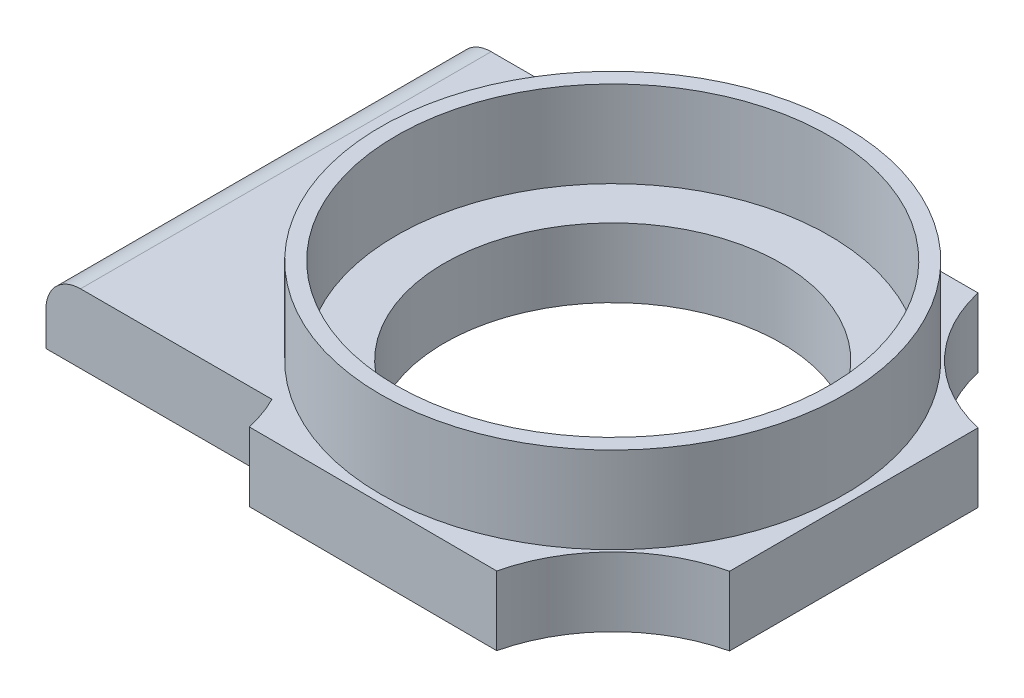
SolidWorks part; units mm, degrees
material "PLA"
ref_plane "Alzado" through (0, 0, 0) normal (0, 0, 1) x (1, 0, 0)
ref_plane "Planta" through (0, 0, 0) normal (0, 1, 0) x (1, 0, 0)
ref_plane "Vista lateral" through (0, 0, 0) normal (1, 0, 0) x (0, 0, -1)
sketch "Croquis1" plane through (0, 0, 0) normal (0, 1, 0) x (1, 0, 0)
  line L48 (-39.6887, -59.3) -> (-105, -59.3)
  line L49 (-36.0808, -69.4967) -> (36.1689, -69.8103)
  line L50 (70, -36.1252) -> (70, 36.1252)
  line L51 (36.1252, 70) -> (-36.1252, 70)
  line L52 (-39.6887, 60) -> (-105, 60)
  line L53 (-28.7652, -39.3) -> (-105, -39.3)
  line L54 (-22.2064, -49.5527) -> (22.4675, -49.7508)
  line L55 (50, -22.3372) -> (50, 22.3372)
  line L56 (22.3372, 50) -> (-22.3372, 50)
  line L57 (-28.7652, 40) -> (-105, 40)
  line L58 (-105, 40) -> (-105, 60)
  line L59 (-105, -59.3) -> (-105, -39.3)
  line L60 (22.4675, -49.7508) -> (22.4675, -69.7508) construction
  line L61 (50, -22.3372) -> (70, -22.3372) construction
  line L62 (22.3372, 50) -> (22.3372, 70) construction
  line L63 (34.1376, -33.9387) -> (48.2491, -48.1114) construction
  line L64 (48.1802, 48.1802) -> (34.0381, 34.0381) construction
  line L65 (-25.3221, 44.8527) -> (-37.611, 64.8945) construction
  line L66 (-37.5773, -64.2895) -> (-25.2453, -44.2725) construction
  arc A16 (-36.0808, -69.4967) -> (-39.6887, -59.3) centre (-80, -79.3) ccw
  arc A17 (70, -36.1252) -> (36.1689, -69.8103) centre (80, -80) ccw
  arc A18 (36.1252, 70) -> (70, 36.1252) centre (80, 80) ccw
  arc A19 (-39.6887, 60) -> (-36.1252, 70) centre (-80, 80) ccw
  arc A20 (-22.2064, -49.5527) -> (-28.7652, -39.3) centre (-80, -79.3) ccw
  arc A21 (50, -22.3372) -> (22.4675, -49.7508) centre (80, -80) ccw
  arc A22 (22.3372, 50) -> (50, 22.3372) centre (80, 80) ccw
  arc A23 (-28.7652, 40) -> (-22.3372, 50) centre (-80, 80) ccw
  point P40 (50, 0)
  dimension "D3" = 76.2348
  dimension "D4" = 72.2504
  dimension "D5" = 44.6744
  dimension "D6" = 45
  dimension "D7" = 65
  dimension "D8" = 50
  dimension "D1" = 65.3113
  dimension "D2" = 20
  dimension "D9" = 105
  dimension "D10" = 119.3
sketch "Croquis2" plane through (0, 0, 0) normal (0, 1, 0) x (1, 0, 0)
  line L117 (-105, 59.8) -> (-105, -59.1)
  line L126 (-105, -59.1) -> (-39.5649, -59.1)
  line L127 (-35.9207, -69.2974) -> (36.0105, -69.6096)
  line L129 (69.8, -35.9659) -> (69.8, 35.9659)
  line L142 (35.9659, 69.8) -> (-35.9659, 69.8)
  line L143 (-39.5649, 59.8) -> (-105, 59.8)
  line L144 (-105, -59.1) -> (-39.5649, -59.1)
  line L145 (-35.9207, -69.2974) -> (36.0105, -69.6096)
  line L146 (69.8, -35.9659) -> (69.8, 35.9659)
  line L147 (35.9659, 69.8) -> (-35.9659, 69.8)
  line L148 (-39.5649, 59.8) -> (-105, 59.8)
  arc A71 (-35.9207, -69.2974) -> (-39.5649, -59.1) centre (-80, -79.3) ccw
  arc A72 (69.8, -35.9659) -> (36.0105, -69.6096) centre (80, -80) ccw
  arc A73 (35.9659, 69.8) -> (69.8, 35.9659) centre (80, 80) ccw
  arc A78 (-39.5649, 59.8) -> (-35.9659, 69.8) centre (-80, 80) ccw
  arc A83 (-35.9207, -69.2974) -> (-39.5649, -59.1) centre (-80, -79.3) ccw
  arc A84 (69.8, -35.9659) -> (36.0105, -69.6096) centre (80, -80) ccw
  arc A85 (35.9659, 69.8) -> (69.8, 35.9659) centre (80, 80) ccw
  arc A86 (-39.5649, 59.8) -> (-35.9659, 69.8) centre (-80, 80) ccw
  dimension "D1" = 0.2
extrude "Saliente-Extruir4" add sketch "Croquis2" along normal blind 20
fillet "Redondeo1" radius 10 1 edges at (-105, 20, -0.35)
sketch "Croquis3" plane through (0, 20, 0) normal (0, 1, 0) x (1, 0, 0)
  circle A0 centre (0, 0) radius 34.95
  dimension "D1" = 69.9
extrude "Saliente-Extruir5" [suppressed] add sketch "Croquis3" along normal blind 24.15
sketch "Croquis4" plane through (0, 0, 0) normal (0, -1, 0) x (1, 0, 0)
  line L1 (-105, 59.3) -> (-105, 39.3) construction
  line L2 (-95.2, 49.3) -> (-37.7649, 49.3) construction
  line L3 (-105, 59.1) -> (-39.5649, 59.1) construction
  line L4 (-27.1207, 60.4974) -> (27.2105, 60.4974) construction
  line L9 (-95.2, -50) -> (-37.7649, -50) construction
  line L10 (-27.1659, -61) -> (27.1659, -61) construction
  line L11 (61, 27.1659) -> (61, -27.1659) construction
  line L12 (-105, -59.8) -> (-105, 59.1) construction
  line L13 (-39.5649, -59.8) -> (-105, -59.8) construction
  line L14 (35.9659, -69.8) -> (-35.9659, -69.8) construction
  line L15 (69.8, 35.9659) -> (69.8, -35.9659) construction
  line L16 (-95.2, 54.2) -> (-95.2, 44.4) construction
  line L17 (-100.1, 49.3) -> (-90.3, 49.3) construction
  circle A0 centre (-95.2, 49.3) radius 4.9
  circle A1 centre (-66.4824, 49.3) radius 4.9
  circle A2 centre (-37.7649, 49.3) radius 4.9
  circle A3 centre (-27.1207, 60.4974) radius 4.9
  circle A4 centre (0.0449, 60.4974) radius 4.9
  circle A5 centre (27.2105, 60.4974) radius 4.9
  circle A6 centre (39.879, 39.5473) radius 4.9
  circle A7 centre (61, 27.1659) radius 4.9
  circle A8 centre (61, 0) radius 4.9
  circle A9 centre (61, -27.1659) radius 4.9
  circle A10 centre (39.7532, -39.7532) radius 4.9
  circle A11 centre (27.1659, -61) radius 4.9
  circle A12 centre (0, -61) radius 4.9
  circle A13 centre (-27.1659, -61) radius 4.9
  circle A14 centre (-37.7649, -50) radius 4.9
  circle A15 centre (-66.4824, -50) radius 4.9
  circle A16 centre (-95.2, -50) radius 4.9
  arc A17 (27.2105, 60.4974) -> (61, 27.1659) centre (74.8518, 75.0007) ccw
  arc A18 (27.1659, -61) -> (61, -27.1659) centre (74.9672, -74.9672) cw
  point P40 (0.0449, 60.4974)
  point P42 (-66.4824, 49.3)
  point P44 (-66.4824, 49.3)
  dimension "D1" = 9.8
  dimension "D19" = 49.8
  dimension "D2" = 9.8
  dimension "D3" = 9.8
  dimension "D4" = 1.8
  dimension "D5" = 8.8
  dimension "D6" = 8.8
  dimension "D7" = 8.8
  dimension "D8" = 8.8
  dimension "D9" = 8.8
  dimension "D10" = 8.8
  dimension "D11" = 8.8
  dimension "D12" = 8.8
  dimension "D13" = 8.8
  dimension "D14" = 8.8
  dimension "D15" = 8.8
  dimension "D16" = 9.8
  dimension "D17" = 9.8
  dimension "D18" = 9.8
extrude "Saliente-Extruir6" [suppressed] add sketch "Croquis4" along normal blind 19.84 contours A5 | A4 | A3 | A2 | A1 | A0 | A17 A6 | A6 A17 | A7 | A8 | A9 | A10 A18 | A18 A10 | A11 | A12 | A13 | A14 | A15 | A16
sketch "Croquis5" plane through (0, 0, 0) normal (0, -1, 0) x (1, 0, 0)
  line L1 (28.33, 28.33) -> (-28.33, 28.33)
  line L2 (28.33, 28.33) -> (28.33, -28.33)
  line L3 (28.33, -28.33) -> (-28.33, -28.33)
  line L4 (-28.33, 28.33) -> (-28.33, -28.33)
  line L5 (28.33, 28.33) -> (-28.33, -28.33) construction
  line L6 (28.33, -28.33) -> (-28.33, 28.33) construction
  point P0 (0, 0)
  dimension "D1" = 56.66
extrude "Cortar-Extruir1" [suppressed] cut sketch "Croquis5" against normal blind 16 contours L2 L1 L4 L3
sketch "Croquis6" [suppressed] plane through (0, 44.15, 0) normal (0, 1, 0) x (1, 0, 0)
  circle A2 centre (0, 0) radius 24.95
  circle A3 centre (0, 0) radius 24.95
  dimension "D1" = 10
extrude "Cortar-Extruir2" [suppressed] cut sketch "Croquis6" against normal through all
extrude "Cortar-Extruir3" cut sketch "Croquis4<3>" against normal blind 10 contours A5 | A6 A17 | A17 A6 | A7 | A8 | A9 | A10 A18 | A18 A10 | A11 | A12 | A13 | A14 | A15 | A16 | A0 | A1 | A2 | A3 | A4 region at (-95.2, 0, 49.3) region at (-66.4824, 0, 49.3) region at (-37.7649, 0, 49.3) region at (-27.1207, 0, 60.4974) region at (0.0449, 0, 60.4974) region at (31.1049, 0, 57.7579) region at (61.7846, 0, 31.8622) region at (41.3695, 0, 41.0583) region at (38.4495, 0, 38.0981) region at (61, 0, 0) region at (61.7903, 0, -31.8613) region at (31.0449, 0, -58.2387) region at (41.254, 0, -41.254) region at (38.3139, 0, -38.3139) region at (0, 0, -61) region at (-27.1659, 0, -61) region at (-37.7649, 0, -50) region at (-66.4824, 0, -50) region at (-95.2, 0, -50)
sketch "Croquis4<3>" plane through (0, 0, 0) normal (0, -1, 0) x (1, 0, 0) same geometry as "Croquis4"
sketch "Croquis7" plane through (0, 20, 0) normal (0, 1, 0) x (1, 0, 0)
  circle A0 centre (0, 0) radius 62.67
  circle A1 centre (0, 0) radius 67.17
  dimension "D1" = 125.34
  dimension "D2" = 4.5
extrude "Saliente-Extruir7" add sketch "Croquis7" along normal blind 25 contours A1 A0 region at (-65.2701, 20, 0)
sketch "Croquis8" plane through (0, 20, 0) normal (0, 1, 0) x (1, 0, 0)
  circle A0 centre (0, 0) radius 48.75
  dimension "D1" = 97.5
extrude "Cortar-Extruir4" cut sketch "Croquis8" against normal through all
